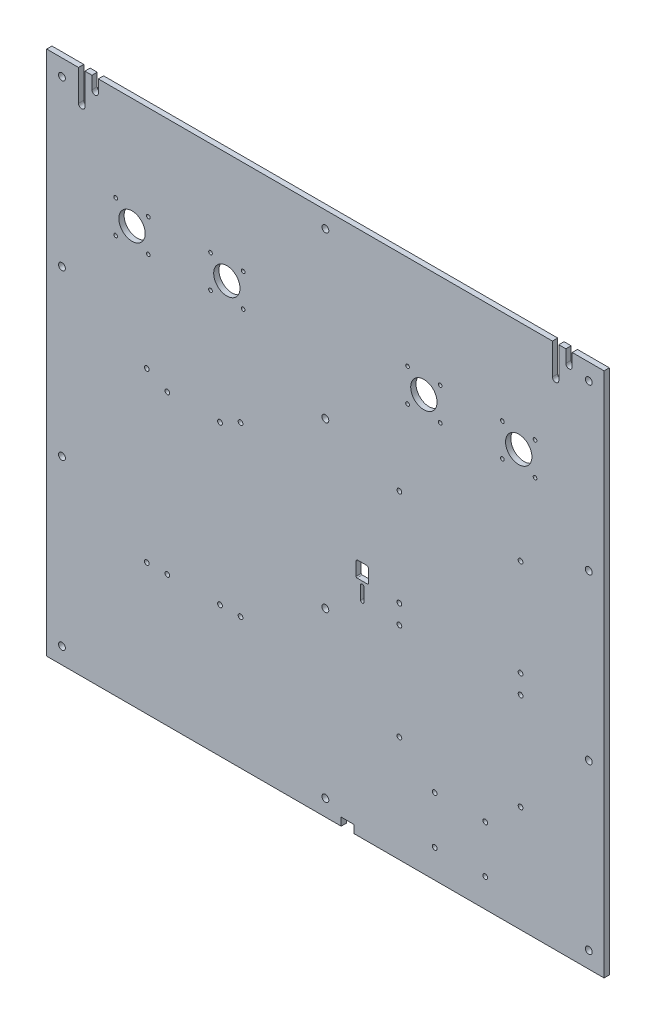
SolidWorks part; units mm, degrees
material "Acrylic (Medium-high impact)"
ref_plane "Front Plane" through (0, 0, 0) normal (0, 0, 1) x (1, 0, 0)
ref_plane "Top Plane" through (0, 0, 0) normal (0, 1, 0) x (1, 0, 0)
ref_plane "Right Plane" through (0, 0, 0) normal (1, 0, 0) x (0, 0, -1)
sketch "Model" plane through (0, 0, 0) normal (0, 0, 1) x (1, 0, 0)
  line L0 (40, -38) -> (30, -38)
  line L1 (29, -37) -> (29, -25)
  line L2 (31, -23) -> (39, -23)
  line L3 (41, -25) -> (41, -37)
  line L4 (-234.25, 220) -> (-234.25, 249.5)
  line L5 (-234.25, 249.5) -> (-264.5, 249.5)
  line L6 (-264.5, 249.5) -> (-264.5, -249.5)
  line L7 (-264.5, -249.5) -> (15, -249.5)
  line L8 (15, -249.5) -> (15, -242)
  line L9 (15, -242) -> (27, -242)
  line L10 (27, -242) -> (27, -249.5)
  line L11 (27, -249.5) -> (264.5, -249.5)
  line L12 (264.5, -249.5) -> (264.5, 249.5)
  line L13 (264.5, 249.5) -> (234.25, 249.5)
  line L14 (234.25, 249.5) -> (234.25, 237.5)
  line L15 (228.25, 237.5) -> (228.25, 249.5)
  line L16 (228.25, 249.5) -> (221.5, 249.5)
  line L17 (221.5, 249.5) -> (221.5, 220)
  line L18 (215.5, 220) -> (215.5, 249.5)
  line L19 (215.5, 249.5) -> (-215.5, 249.5)
  line L20 (-215.5, 249.5) -> (-215.5, 237.5)
  line L21 (-221.5, 237.5) -> (-221.5, 249.5)
  line L22 (-221.5, 249.5) -> (-228.25, 249.5)
  line L23 (-228.25, 249.5) -> (-228.25, 220)
  line L24 (36.6, -42) -> (36.6, -54.5)
  line L25 (33.4, -54.5) -> (33.4, -42)
  circle A0 centre (0, 234) radius 3.25
  circle A1 centre (250, 78) radius 3.25
  circle A2 centre (250, -234) radius 3.25
  circle A3 centre (250, -78) radius 3.25
  circle A4 centre (151.75, -177.5) radius 2.25
  circle A5 centre (0, -234) radius 3.25
  circle A6 centre (0, -78) radius 3.25
  circle A7 centre (0, 78) radius 3.25
  circle A8 centre (70.25, -38.5) radius 2.25
  circle A9 centre (185.25, -56.5) radius 2.25
  circle A10 centre (185.25, -148.5) radius 2.25
  circle A11 centre (70.25, -148.5) radius 2.25
  circle A12 centre (70.25, -56.5) radius 2.25
  circle A13 centre (70.25, 53.5) radius 2.25
  circle A14 centre (185.25, 53.5) radius 2.25
  circle A15 centre (185.25, -38.5) radius 2.25
  circle A16 centre (199, 160) radius 1.75
  circle A17 centre (199, 129) radius 1.75
  circle A18 centre (168, 129) radius 1.75
  circle A19 centre (168, 160) radius 1.75
  circle A20 centre (109, 160) radius 1.75
  circle A21 centre (78, 129) radius 1.75
  circle A22 centre (78, 160) radius 1.75
  circle A23 centre (109, 129) radius 1.75
  circle A24 centre (-109, 129) radius 1.75
  circle A25 centre (-109, 160) radius 1.75
  circle A26 centre (-78, 129) radius 1.75
  circle A27 centre (-78, 160) radius 1.75
  circle A28 centre (-199, 129) radius 1.75
  circle A29 centre (-168, 129) radius 1.75
  circle A30 centre (-168, 160) radius 1.75
  circle A31 centre (-199, 160) radius 1.75
  circle A32 centre (-250, 78) radius 3.25
  circle A33 centre (-250, -78) radius 3.25
  circle A34 centre (-250, -234) radius 3.25
  circle A35 centre (-250, 234) radius 3.25
  circle A36 centre (-100, -125) radius 2.25
  circle A37 centre (-100, 25) radius 2.25
  circle A38 centre (-150, 25) radius 2.25
  circle A39 centre (250, 234) radius 3.25
  circle A40 centre (-150, -125) radius 2.25
  circle A41 centre (103.75, -177.5) radius 2.25
  circle A42 centre (-183.5, 144.5) radius 12.5
  circle A45 centre (-93.5, 144.5) radius 12.5
  circle A46 centre (93.5, 144.5) radius 12.5
  circle A49 centre (183.5, 144.5) radius 12.5
  circle A50 centre (-169.5, -125) radius 2.25
  circle A51 centre (-80.5, 34.5) radius 2.25
  circle A52 centre (-169.5, 34.5) radius 2.25
  circle A53 centre (-80.5, -125) radius 2.25
  circle A54 centre (151.75, -222.4991) radius 2.25
  circle A55 centre (103.75, -222.4991) radius 2.25
  arc A56 (40, -38) -> (41, -37) centre (40, -37) ccw
  arc A57 (29, -37) -> (30, -38) centre (30, -37) ccw
  arc A58 (31, -23) -> (29, -25) centre (31, -25) ccw
  arc A59 (41, -25) -> (39, -23) centre (39, -25) ccw
  arc A60 (-234.25, 220) -> (-228.25, 220) centre (-231.25, 220) ccw
  arc A61 (228.25, 237.5) -> (234.25, 237.5) centre (231.25, 237.5) ccw
  arc A62 (215.5, 220) -> (221.5, 220) centre (218.5, 220) ccw
  arc A63 (-221.5, 237.5) -> (-215.5, 237.5) centre (-218.5, 237.5) ccw
  arc A64 (36.6, -42) -> (33.4, -42) centre (35, -42) ccw
  arc A65 (33.4, -54.5) -> (36.6, -54.5) centre (35, -54.5) ccw
  point P86 (0, 0)
  dimension "D1" = 6.5
  dimension "D2" = 3.5
  dimension "D3" = 4.5
  dimension "D4" = 12.5
  dimension "D5" = 1
  dimension "D6" = 2
  dimension "D7" = 3
  dimension "D8" = 1.6
  dimension "D28" = 25
  dimension "D47" = 25
  dimension "D51" = 183.5
  dimension "D52" = 218.5
  dimension "D53" = 264.5
  dimension "D54" = 23
  dimension "D9" = 15
  dimension "D10" = 27
  dimension "D11" = 35
  dimension "D12" = 41
  dimension "D13" = 70.25
  dimension "D14" = 78
  dimension "D15" = 93.5
  dimension "D16" = 103.75
  dimension "D17" = 109
  dimension "D18" = 151.75
  dimension "D19" = 168
  dimension "D20" = 12
  dimension "D21" = 185.25
  dimension "D22" = 199
  dimension "D23" = 250
  dimension "D24" = 78
  dimension "D25" = 80.5
  dimension "D26" = 15
  dimension "D27" = 93.5
  dimension "D29" = 100
  dimension "D30" = 109
  dimension "D31" = 150
  dimension "D32" = 168
  dimension "D33" = 169.5
  dimension "D34" = 183.5
  dimension "D35" = 199
  dimension "D36" = 218.5
  dimension "D37" = 231.25
  dimension "D38" = 250
  dimension "D39" = 264.5
  dimension "D40" = 25
  dimension "D41" = 34.5
  dimension "D42" = 53.5
  dimension "D43" = 78
  dimension "D44" = 129
  dimension "D45" = 237.5
  dimension "D46" = 242
  dimension "D48" = 160
  dimension "D49" = 220
  dimension "D50" = 234
  dimension "D55" = 38.5
  dimension "D56" = 42
  dimension "D57" = 54.5
  dimension "D58" = 56.5
  dimension "D59" = 78
  dimension "D60" = 125
  dimension "D61" = 148.5
  dimension "D62" = 177.5
  dimension "D63" = 222.4991
  dimension "D64" = 234
  dimension "D66" = 249.5
  dimension "D70" = 144.5
extrude "Boss-Extrude1" add sketch "Model" along normal blind 5
